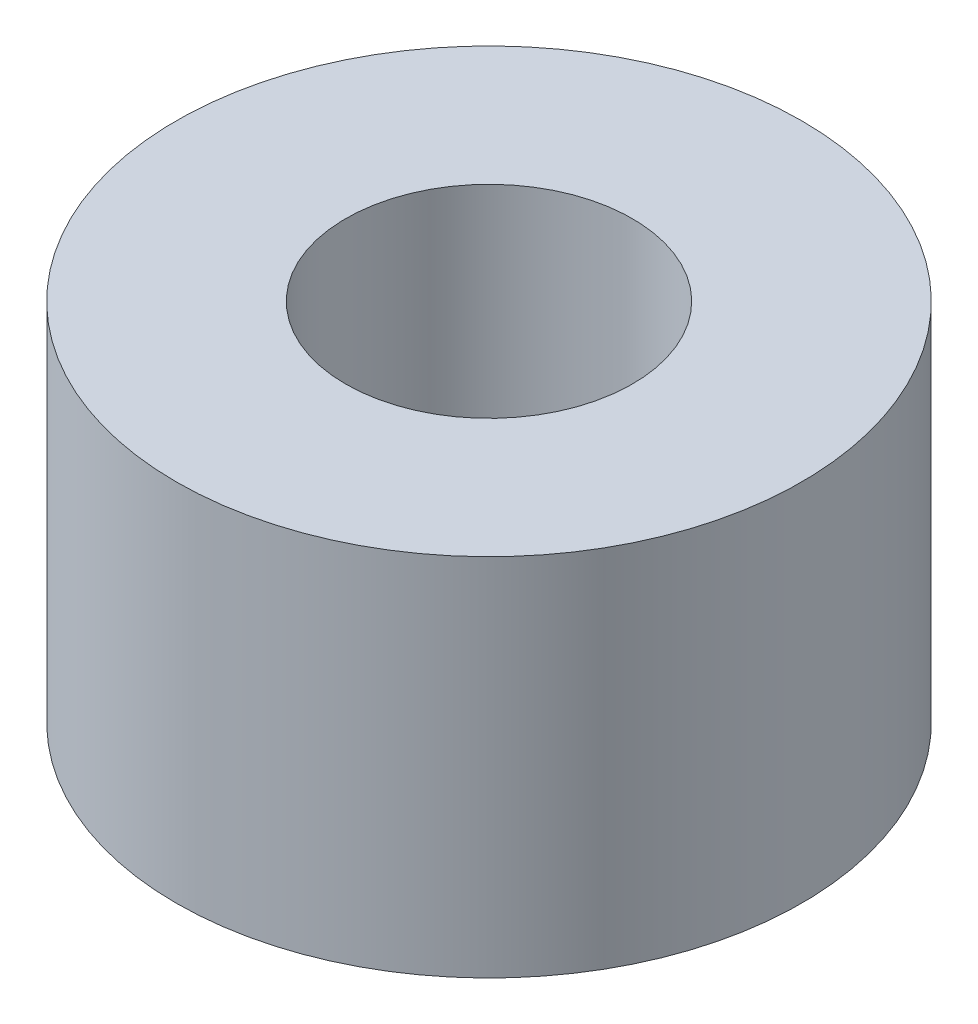
SolidWorks part; units mm, degrees
material "PS Medium/High Flow"
ref_plane "Front Plane" through (0, 0, 0) normal (0, 0, 1) x (1, 0, 0)
ref_plane "Top Plane" through (0, 0, 0) normal (0, 1, 0) x (1, 0, 0)
ref_plane "Right Plane" through (0, 0, 0) normal (1, 0, 0) x (0, 0, -1)
ref_axis "Axis X" through (57.4134, 0, 0) along (-1, 0, 0)
ref_axis "Axis Y" through (0, 65.1338, 0) along (0, -1, 0)
ref_axis "Axis Z" through (0, 0, -90.83) along (0, 0, 1)
sketch "Sketch1" plane through (0, 0, 0) normal (0, 1, 0) x (1, 0, 0)
  circle A0 centre (0, 0) radius 2.4
  circle A1 centre (0, 0) radius 1.1
  dimension "D1" = 2.2
  dimension "D2" = 4.8
extrude "Boss-Extrude1" add sketch "Sketch1" along normal blind 2.8
